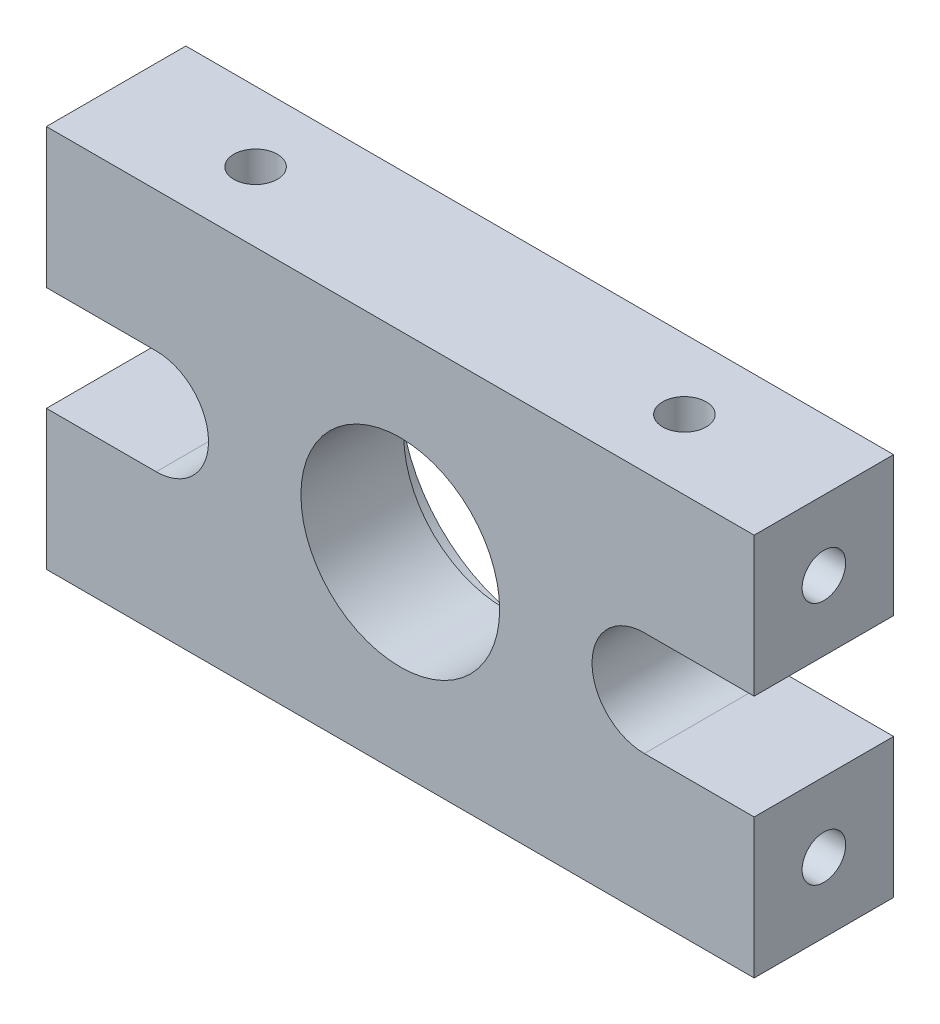
SolidWorks part; units mm, degrees
ref_plane "Front Plane" through (0, 0, 0) normal (0, 0, 1) x (1, 0, 0)
ref_plane "Top Plane" through (0, 0, 0) normal (0, 1, 0) x (1, 0, 0)
ref_plane "Right Plane" through (0, 0, 0) normal (1, 0, 0) x (0, 0, -1)
sketch "Sketch1" plane through (0, 0, 0) normal (0, 0, 1) x (1, 0, 0)
  line L0 (0, 0) -> (40.6, 0)
  line L1 (40.6, 0) -> (40.6, 8)
  line L2 (40.6, 22) -> (0, 22)
  line L3 (0, 8) -> (0, 0)
  line L4 (0, 8) -> (6.3, 8)
  line L5 (6.3, 14) -> (0, 14)
  line L6 (0, 14) -> (0, 22)
  line L7 (40.6, 8) -> (34.3, 8)
  line L8 (34.3, 14) -> (40.6, 14)
  line L9 (40.6, 14) -> (40.6, 22)
  circle A0 centre (20.3, 11) radius 5.7
  arc A1 (6.3, 8) -> (6.3, 14) centre (6.3, 11) ccw
  arc A2 (34.3, 8) -> (34.3, 14) centre (34.3, 11) cw
  dimension "D1" = 11.4
  dimension "D6" = 3
  dimension "D2" = 40.6
  dimension "D3" = 22
  dimension "D4" = 11
  dimension "D5" = 20.3
  dimension "D7" = 6.3
extrude "Boss-Extrude1" add sketch "Sketch1" along normal blind 8
hole_wizard "Tap Drill for M3x0.5 Tap1" positions "Sketch3" profile "Sketch2" hole size "M3x0.5" standard "ANSI Metric"
sketch "Sketch3" plane through (40.6, 0, 0) normal (1, 0, 0) x (0, 0, -1)
  line L0 (-8, 0) -> (-8, 8) construction
  line L1 (-8, 0) -> (0, 0) construction
  line L2 (-8, 22) -> (0, 22) construction
  point P0 (-4, 18)
  point P2 (-4, 4)
  dimension "D1" = 4
  dimension "D2" = 4
  dimension "D3" = 4
sketch "Sketch2" plane through (40.6, 18, 4) normal (0, 1, 0) x (0, 0, -1)
  line L0 (0, 0) -> (0, 5.7511)
  line L1 (0, 5.7511) -> (1.25, 5)
  line L2 (1.25, 5) -> (1.25, 0)
  line L5 (1.25, 0) -> (0, 0)
  line L10 (0, 5.7511) -> (-1.25, 5) construction
  line L11 (0, -6.35) -> (0, 107.95) construction
  dimension "Hole Dia." = 2.5
  dimension "Hole Depth" = 5
  dimension "Drill Angle" = 118
hole_wizard "Tap Drill for M3x0.5 Tap2" positions "Sketch5" profile "Sketch4" hole size "M3x0.5" standard "ANSI Metric"
sketch "Sketch5" plane through (0, 0, 0) normal (-1, 0, 0) x (0, 0, 1)
  line L0 (8, 22) -> (8, 14) construction
  line L1 (8, 22) -> (0, 22) construction
  line L2 (8, 0) -> (0, 0) construction
  point P0 (4, 4)
  point P2 (4, 18)
  dimension "D1" = 4
  dimension "D2" = 4
  dimension "D3" = 4
sketch "Sketch4" plane through (0, 4, 4) normal (0, 1, 0) x (0, 0, 1)
  line L0 (0, 0) -> (0, 5.7511)
  line L1 (0, 5.7511) -> (1.25, 5)
  line L2 (1.25, 5) -> (1.25, 0)
  line L5 (1.25, 0) -> (0, 0)
  line L10 (0, 5.7511) -> (-1.25, 5) construction
  line L11 (0, -6.35) -> (0, 107.95) construction
  dimension "Hole Dia." = 2.5
  dimension "Hole Depth" = 5
  dimension "Drill Angle" = 118
hole_wizard "Tap Drill for M3x0.5 Tap3" positions "Sketch7" profile "Sketch6" hole size "M3x0.5" standard "ANSI Metric"
sketch "Sketch7" plane through (0, 22, 0) normal (0, 1, 0) x (1, 0, 0)
  line L0 (0, -8) -> (0, 0) construction
  line L1 (40.6, 0) -> (0, 0) construction
  line L2 (40.6, -8) -> (40.6, 0) construction
  point P0 (32.6, -4)
  point P2 (8, -4)
  dimension "D1" = 8
  dimension "D2" = 4
  dimension "D3" = 8
sketch "Sketch6" plane through (32.6, 22, 4) normal (1, 0, 0) x (0, 0, 1)
  line L0 (0, 0) -> (0, 5.7511)
  line L1 (0, 5.7511) -> (1.25, 5)
  line L2 (1.25, 5) -> (1.25, 0)
  line L5 (1.25, 0) -> (0, 0)
  line L10 (0, 5.7511) -> (-1.25, 5) construction
  line L11 (0, -6.35) -> (0, 107.95) construction
  dimension "Hole Dia." = 2.5
  dimension "Hole Depth" = 5
  dimension "Drill Angle" = 118
sketch "Sketch8" plane through (0, 0, 0) normal (0, 0, -1) x (-1, 0, 0)
  circle A0 centre (-20.3, 11) radius 8
  dimension "D1" = 16
extrude "Cut-Extrude1" cut sketch "Sketch8" against normal blind 2.1
